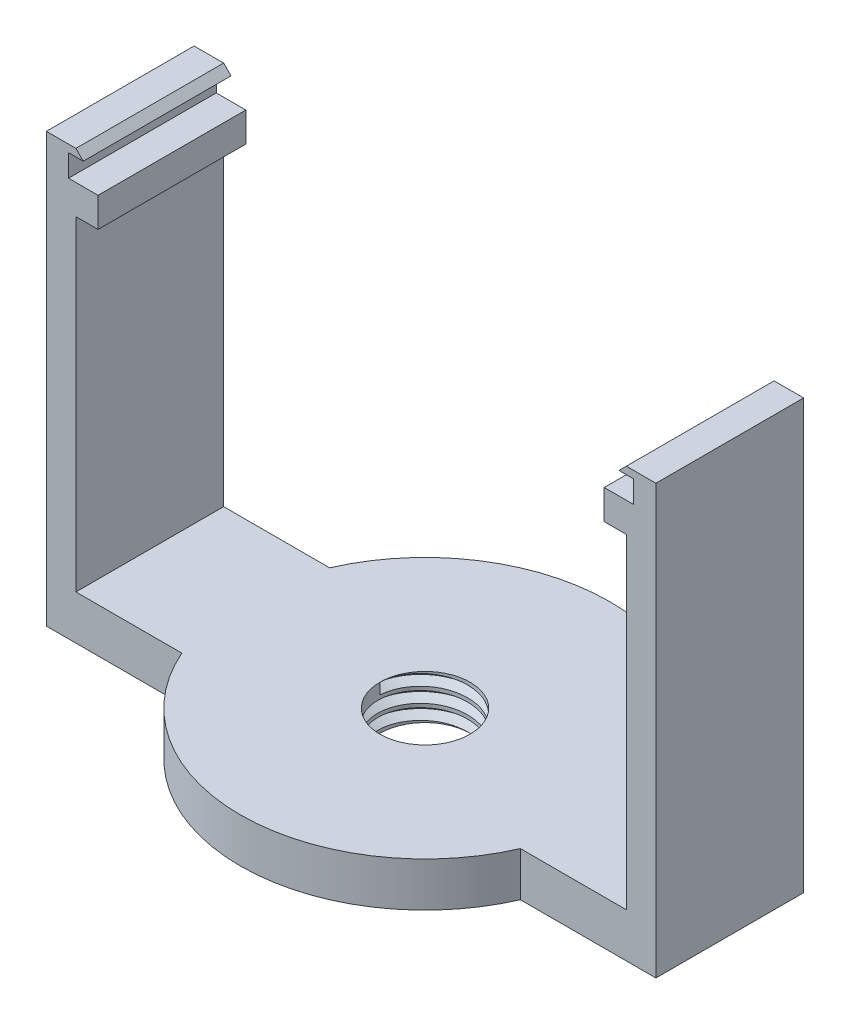
SolidWorks part; units mm, degrees
material "ABS"
ref_plane "Front Plane" through (0, 0, 0) normal (0, 0, 1) x (1, 0, 0)
ref_plane "Top Plane" through (0, 0, 0) normal (0, 1, 0) x (1, 0, 0)
ref_plane "Right Plane" through (0, 0, 0) normal (1, 0, 0) x (0, 0, -1)
sketch "Sketch1" plane through (0, 0, 0) normal (0, 1, 0) x (1, 0, 0)
  line L1 (7.8689, -4.469) -> (6.3689, -4.469)
  line L2 (7.8689, -4.469) -> (7.8689, -14.469)
  line L3 (7.8689, -14.469) -> (6.3689, -14.469)
  line L4 (6.3689, -4.469) -> (6.3689, -14.469)
  line L5 (7.8689, -4.469) -> (9.8689, -4.469)
  line L6 (7.8689, -4.469) -> (7.8689, -14.469)
  line L7 (7.8689, -14.469) -> (9.8689, -14.469)
  line L8 (9.8689, -4.469) -> (9.8689, -14.469)
  line L9 (46.1229, -4.469) -> (47.6229, -4.469)
  line L10 (46.1229, -4.469) -> (46.1229, -14.469)
  line L11 (46.1229, -14.469) -> (47.6229, -14.469)
  line L12 (47.6229, -4.469) -> (47.6229, -14.469)
  line L13 (46.1229, -4.469) -> (44.1229, -4.469)
  line L14 (46.1229, -4.469) -> (46.1229, -14.469)
  line L15 (46.1229, -14.469) -> (44.1229, -14.469)
  line L16 (44.1229, -4.469) -> (44.1229, -14.469)
  point P0 (7.8689, -4.469)
  point P1 (46.1229, -4.469)
  dimension "D1" = 38.254
  dimension "D2" = 1.5
  dimension "D3" = 10
  dimension "D4" = 2
  dimension "D5" = 10
  dimension "D6" = 1.5
  dimension "D7" = 2
extrude "Boss-Extrude1" add sketch "Sketch1" along normal blind 4 contours L1 L4 L3 L2 | L12 L9 L10 L11 region at (7.1189, 0, 9.469) region at (46.8729, 0, 9.469)
sketch "Sketch3" plane through (0, 0, 0) normal (0, 1, 0) x (1, 0, 0)
  line L1 (7.8689, -4.469) -> (6.3689, -4.469)
  line L2 (7.8689, -4.469) -> (7.8689, -14.469)
  line L3 (7.8689, -14.469) -> (6.3689, -14.469)
  line L4 (6.3689, -4.469) -> (6.3689, -14.469)
  line L5 (7.8689, -4.469) -> (9.8689, -4.469)
  line L6 (7.8689, -4.469) -> (7.8689, -14.469)
  line L7 (7.8689, -14.469) -> (9.8689, -14.469)
  line L8 (9.8689, -4.469) -> (9.8689, -14.469)
  line L9 (46.1229, -4.469) -> (47.6229, -4.469)
  line L10 (46.1229, -4.469) -> (46.1229, -14.469)
  line L11 (46.1229, -14.469) -> (47.6229, -14.469)
  line L12 (47.6229, -4.469) -> (47.6229, -14.469)
  line L13 (46.1229, -4.469) -> (44.1229, -4.469)
  line L14 (46.1229, -4.469) -> (46.1229, -14.469)
  line L15 (46.1229, -14.469) -> (44.1229, -14.469)
  line L16 (44.1229, -4.469) -> (44.1229, -14.469)
  point P0 (7.8689, -4.469)
  point P1 (46.1229, -4.469)
  dimension "D1" = 38.254
  dimension "D2" = 1.5
  dimension "D3" = 10
  dimension "D4" = 2
  dimension "D5" = 10
  dimension "D6" = 1.5
  dimension "D7" = 2
extrude "Boss-Extrude2" add sketch "Sketch3" along normal blind 2 contours L8 L5 L2 L7 | L13 L16 L15 L10 region at (8.8689, 0, 9.469) region at (45.1229, 0, 9.469)
sketch "Sketch4" plane through (0, 0, 0) normal (0, -1, 0) x (1, 0, 0)
  line L0 (9.8689, 4.469) -> (6.3689, 4.469) construction
  line L1 (6.3689, 14.469) -> (8.3689, 14.469)
  line L2 (6.3689, 14.469) -> (6.3689, 4.469)
  line L3 (6.3689, 4.469) -> (8.3689, 4.469)
  line L4 (8.3689, 14.469) -> (8.3689, 4.469)
  line L6 (47.6229, 14.469) -> (45.6229, 14.469)
  line L7 (47.6229, 14.469) -> (47.6229, 4.469)
  line L8 (47.6229, 4.469) -> (45.6229, 4.469)
  line L9 (45.6229, 14.469) -> (45.6229, 4.469)
  line L10 (44.1229, 4.469) -> (47.6229, 4.469) construction
  dimension "D1" = 2
  dimension "D2" = 2
extrude "Boss-Extrude3" add sketch "Sketch4" along normal blind 25
sketch "Sketch5" plane through (8.3689, 0, 0) normal (1, 0, 0) x (0, 0, -1)
  line L0 (-4.469, -25) -> (-4.469, 0) construction
  line L1 (-14.469, -25) -> (-4.469, -25)
  line L2 (-14.469, -25) -> (-14.469, -22)
  line L3 (-14.469, -22) -> (-4.469, -22)
  line L4 (-4.469, -25) -> (-4.469, -22)
  dimension "D1" = 3
extrude "Boss-Extrude4" add sketch "Sketch5" along normal up to surface (37.254 mm away) up to face at (45.6229, -12.5, 9.469)
sketch "Sketch6" plane through (0, -22, 0) normal (0, 1, 0) x (1, 0, 0)
  circle A0 centre (26.9959, -9.469) radius 12.5
  point P2 (26.9959, -9.469)
  dimension "D1" = 25
extrude "Boss-Extrude5" add sketch "Sketch6" against normal blind 3
sketch "Sketch7" plane through (0, -22, 0) normal (0, 1, 0) x (1, 0, 0)
  circle A0 centre (26.9959, -9.469) radius 3.05
  dimension "D1" = 6.1
extrude "Cut-Extrude1" cut sketch "Sketch7" against normal blind 3
thread "Thread1" pitch 1 method cut profile "Thread Profile1" start angle 0, offset 0, length 10, pitch 1, diameter 6.1
ref_plane "Plane1" through (23.9459, -22, 9.469) normal (0, 0, 1) x (-1, 0, 0)
sketch "Thread Profile1" plane through (23.9459, -22, 9.469) normal (0, 0, 1) x (-1, 0, 0)
  line L0 (0, 0) -> (0, 1) construction
  line L1 (0, 0) -> (0.5413, 0.3125)
  line L2 (0.5413, 0.3125) -> (0.5413, 0.4375)
  line L3 (0.5413, 0.4375) -> (0, 0.75)
  line L4 (0.5413, 0.375) -> (0, 0.375) construction
  line L11 (0, 0) -> (0, 0.75)
  point P2 (0, 0)
  dimension "Pitch" = 1
  dimension "Profile_Angle" = 60
  dimension "Profile_Land" = 0.125
  dimension "Profile_Height" = 0.5413
sketch "Sketch8" plane through (7.8689, 0, 0) normal (1, 0, 0) x (0, 0, -1)
  line L0 (-4.469, 4) -> (-4.469, 2) construction
  line L1 (-14.469, 4) -> (-4.469, 4)
  line L2 (-14.469, 4) -> (-14.469, 3.5)
  line L3 (-14.469, 3.5) -> (-4.469, 3.5)
  line L4 (-4.469, 4) -> (-4.469, 3.5)
  dimension "D1" = 0.5
extrude "Boss-Extrude6" add sketch "Sketch8" along normal up to surface (38.254 mm away)
sketch "Sketch9" plane through (0, 0, 14.469) normal (0, 0, 1) x (1, 0, 0)
  line L0 (26.9959, 4) -> (26.9959, 3.5) construction
  line L1 (6.3689, 4) -> (47.6229, 4) construction
  line L2 (46.1229, 3.5) -> (7.8689, 3.5) construction
  line L3 (8.8689, 3.5) -> (8.3689, 4)
  line L5 (40.6689, 4) -> (8.3689, 4)
  line L6 (8.8689, 3.5) -> (40.1689, 3.5)
  line L7 (45.1229, 3.5) -> (45.6229, 4)
  line L8 (45.6229, 4) -> (40.6689, 4)
  line L9 (40.1689, 3.5) -> (45.1229, 3.5)
extrude "Cut-Extrude2" cut sketch "Sketch9" against normal blind 10
